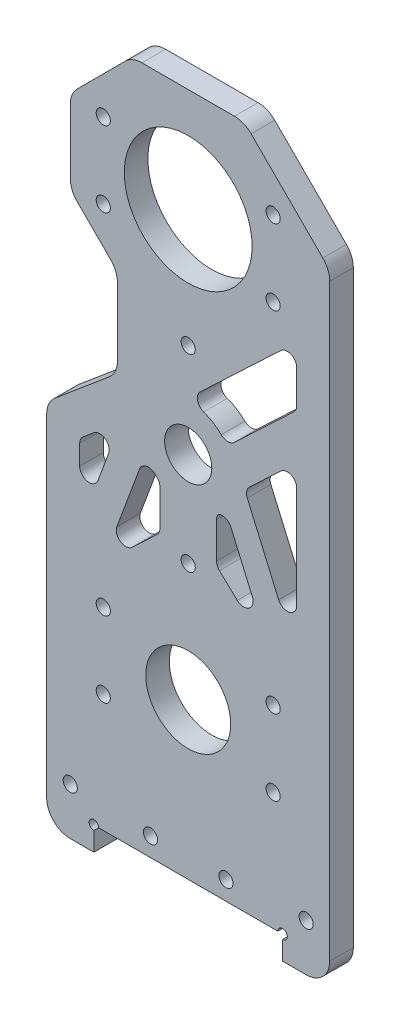
SolidWorks part; units mm, degrees
ref_plane "前视基准面" through (0, 0, 0) normal (0, 0, 1) x (1, 0, 0)
ref_plane "上视基准面" through (0, 0, 0) normal (0, 1, 0) x (1, 0, 0)
ref_plane "右视基准面" through (0, 0, 0) normal (1, 0, 0) x (0, 0, -1)
other "Configuration Table"
sketch "草图1" plane through (0, 0, 0) normal (0, 0, 1) x (1, 0, 0)
  line L1 (30, 0) -> (-30, 0)
  line L2 (30, 0) -> (30, 150)
  line L3 (30, 150) -> (-30, 150)
  line L4 (-30, 0) -> (-30, 150)
  point P6 (0, 0)
  dimension "D1" = 60
  dimension "D2" = 150
extrude "凸台-拉伸1" add sketch "草图1" along normal blind 5
sketch "草图2" plane through (0, 0, 5) normal (0, 0, 1) x (1, 0, 0)
  line L0 (-30, 0) -> (30, 0) construction
  line L1 (-20, 0) -> (20, 0)
  line L2 (-20, 0) -> (-20, 5)
  line L3 (-20, 5) -> (20, 5)
  line L4 (20, 0) -> (20, 5)
  line L5 (-25, 10) -> (25, 10) construction
  line L6 (-30, 150) -> (-30, 0) construction
  line L7 (30, 0) -> (30, 150) construction
  line L8 (0, 0) -> (0, 9) construction
  line L9 (-8, 9) -> (8, 9) construction
  circle A0 centre (-25, 10) radius 1.5
  circle A1 centre (25, 10) radius 1.5
  circle A2 centre (20, 5) radius 1
  circle A3 centre (-20, 5) radius 1
  circle A4 centre (8, 9) radius 1.5
  circle A5 centre (-8, 9) radius 1.5
  point P21 (0, 9)
  dimension "D1" = 3
  dimension "D3" = 2
  dimension "D10" = 3
  dimension "D2" = 5
  dimension "D4" = 10
  dimension "D5" = 10
  dimension "D6" = 5
  dimension "D7" = 5
  dimension "D8" = 10
  dimension "D9" = 16
  dimension "D11" = 4
extrude "切除-拉伸1" cut sketch "草图2" against normal blind 5
sketch "草图4" plane through (0, 0, 5) normal (0, 0, 1) x (1, 0, 0)
  line L0 (0, 0) -> (0, 150) construction
  line L1 (30, 150) -> (-30, 150) construction
  line L2 (-19, 5) -> (19, 5) construction
  circle A0 centre (0, 128) radius 13.55
  circle A1 centre (0, 38) radius 9
  dimension "D1" = 90
  dimension "D2" = 27.1
  dimension "D4" = 18
  dimension "D3" = 33
extrude "弹链孔" cut sketch "草图4" against normal through all
sketch "草图5" plane through (0, 0, 5) normal (0, 0, 1) x (1, 0, 0)
  line L0 (-19.1511, 111.9303) -> (-15, 106.9832) construction
  line L1 (-30, 150) -> (-30, 0) construction
  line L2 (-15, 106.9832) -> (-15, 90.3497)
  line L3 (-15, 90.3497) -> (-30, 77.7632)
  line L4 (-30, 124.8595) -> (-19.1511, 111.9303) construction
  line L5 (30, 150) -> (-30, 150) construction
  line L6 (-30, 124.8595) -> (-30, 77.7632)
  line L7 (-30, 124.8595) -> (-30, 150)
  line L8 (-30, 150) -> (-11.8743, 150)
  line L9 (0, 128) -> (-19.1511, 111.9303) construction
  line L10 (-19.1511, 111.9303) -> (-65.3229, 73.1876) construction
  line L11 (-52.9813, 58.4796) -> (-30, 77.7632) construction
  line L12 (-65.3229, 73.1876) -> (-52.9813, 58.4796) construction
  line L13 (-22, 116.1257) -> (-15, 109.1257)
  line L14 (-22, 116.1257) -> (-22, 139.8743) construction
  line L15 (-22, 139.8743) -> (-11.8743, 150)
  line L16 (-15, 109.1257) -> (-15, 106.9832)
  line L17 (11.8743, 150) -> (30, 131.8743)
  line L18 (30, 0) -> (30, 150) construction
  line L19 (11.8743, 150) -> (30, 150)
  line L20 (30, 150) -> (30, 131.8743)
  line L21 (-22, 139.8743) -> (-25, 136.8743)
  line L22 (-25, 136.8743) -> (-25, 119.1257)
  line L23 (-22, 116.1257) -> (-25, 119.1257)
  arc A0 (-11.8743, 150) -> (-19.1511, 111.9303) centre (0, 128) ccw construction
  dimension "D1" = 40
  dimension "D2" = 25
  dimension "D3" = 15
  dimension "D4" = 30
  dimension "D5" = 19.2
  dimension "D6" = 135
  dimension "D7" = 135
  dimension "D8" = 45
extrude "切除-拉伸2" cut sketch "草图5" against normal through all
sketch "草图6" plane through (0, 0, 5) normal (0, 0, 1) x (1, 0, 0)
  line L0 (0, 83) -> (0, 128) construction
  circle A0 centre (0, 83) radius 5
  dimension "D2" = 10
  dimension "D1" = 45
extrude "切除-拉伸3" cut sketch "草图6" against normal through all
sketch "草图7" plane through (0, 0, 5) normal (0, 0, 1) x (1, 0, 0)
  line L0 (0, 63) -> (0, 103) construction
  line L1 (-18, 136) -> (18, 136) construction
  line L2 (-18, 136) -> (-18, 120) construction
  line L3 (-18, 120) -> (18, 120) construction
  line L4 (18, 136) -> (18, 120) construction
  line L5 (-18, 136) -> (18, 120) construction
  line L6 (-18, 120) -> (18, 136) construction
  line L8 (-18, 46) -> (18, 46) construction
  line L9 (-18, 46) -> (-18, 30) construction
  line L10 (-18, 30) -> (18, 30) construction
  line L11 (18, 46) -> (18, 30) construction
  line L12 (-18, 46) -> (18, 30) construction
  line L13 (-18, 30) -> (18, 46) construction
  circle A0 centre (18, 136) radius 1.5
  circle A1 centre (-18, 136) radius 1.5
  circle A2 centre (-18, 120) radius 1.5
  circle A3 centre (18, 120) radius 1.5
  circle A4 centre (0, 63) radius 1.5
  circle A6 centre (0, 103) radius 1.5
  circle A7 centre (0, 83) radius 5 construction
  circle A8 centre (-18, 46) radius 1.5
  circle A9 centre (-18, 30) radius 1.5
  circle A10 centre (18, 46) radius 1.5
  circle A11 centre (18, 30) radius 1.5
  point P0 (0, 128)
  point P14 (0, 83)
  point P19 (0, 38)
  dimension "D3" = 3
  dimension "D5" = 3
  dimension "D8" = 3
  dimension "D1" = 36
  dimension "D2" = 16
  dimension "D4" = 40
  dimension "D6" = 36
  dimension "D7" = 16
extrude "切除-拉伸4" cut sketch "草图7" against normal through all
sketch "草图8" plane through (0, 0, 0) normal (0, 0, -1) x (-1, 0, 0)
  circle A0 centre (-18, 136) radius 4.5
  circle A1 centre (18, 136) radius 4.5
  circle A2 centre (-18, 120) radius 4.5
  circle A3 centre (18, 120) radius 4.5
  circle A4 centre (0, 103) radius 4.5
  circle A5 centre (0, 63) radius 4.5
  dimension "D1" = 9
extrude "切除-拉伸5" cut sketch "草图8" against normal blind 2
sketch "草图9" plane through (0, 0, 5) normal (0, 0, 1) x (1, 0, 0)
  line L0 (-9.6216, 85.7248) -> (-23, 74.499)
  line L1 (-23, 74.499) -> (-23, 49.5307)
  line L3 (-23, 49.5307) -> (-6, 65.5863)
  line L7 (6, 65.5863) -> (23, 49.5307)
  line L8 (23, 49.5307) -> (23, 92.9752)
  line L10 (8.241, 88.6645) -> (23, 102.6036)
  line L11 (23, 102.6036) -> (23, 115.0938)
  line L12 (23, 115.0938) -> (-0.402, 92.9919)
  line L13 (0, 63) -> (-18, 46) construction
  line L14 (-30, 77.7632) -> (-15, 90.3497) construction
  line L15 (-30, 77.7632) -> (-30, 0) construction
  line L16 (0, 83) -> (0, 63) construction
  line L17 (-6, 83) -> (-6, 63)
  line L18 (6, 83) -> (6, 63)
  line L19 (0, 63) -> (18, 46) construction
  line L20 (30, 0) -> (30, 131.8743) construction
  line L21 (23, 92.9752) -> (9.6461, 80.3631)
  line L22 (0, 103) -> (18, 120) construction
  line L23 (9.6461, 80.3631) -> (23, 49.5307) construction
  line L24 (6.8932, 79.1708) -> (20.2471, 48.3384)
  line L25 (12.399, 81.5554) -> (25.7529, 50.723)
  line L26 (12.399, 81.5554) -> (11.9663, 82.5544)
  line L27 (-9.6216, 85.7248) -> (-23, 49.5307) construction
  line L28 (-12.4355, 86.765) -> (-25.8139, 50.5708)
  line L29 (-6.8077, 84.6847) -> (-20.1861, 48.4906)
  circle A2 centre (0, 83) radius 10
  dimension "D1" = 6
  dimension "D4" = 20
  dimension "D2" = 7
  dimension "D3" = 7
  dimension "D7" = 6
  dimension "D8" = 7
  dimension "D9" = 7
  dimension "D10" = 7
  dimension "D11" = 7
  dimension "D5" = 6
  dimension "D6" = 6
  dimension "D12" = 3
  dimension "D13" = 3
  dimension "D14" = 3
  dimension "D15" = 3
extrude "切除-拉伸6" cut sketch "草图9" against normal through all contours L28 L0 L1 | A2 L29 L3 L17 | A2 L18 L7 L24 | L26 L25 L8 L21 | A2 L10 L11 L12
fillet "圆角3" radius 2 18 edges at (-6, 75, 2.5) (-6, 65.5863, 2.5) (-18.0863, 54.1715, 2.5) (-9.0235, 78.69, 2.5) (-0.402, 92.9919, 2.5) (23, 115.0938, 2.5) (23, 102.6036, 2.5) (8.241, 88.6645, 2.5) (-23, 58.1837, 2.5) (-14.258, 81.8345, 2.5) (11.9663, 82.5544, 2.5) (23, 92.9752, 2.5) (23, 57.0791, 2.5) (7.8937, 76.8608, 2.5) (17.4677, 54.7557, 2.5) (6, 65.5863, 2.5) (6, 75, 2.5) (-23, 74.499, 2.5)
fillet "圆角4" radius 5 10 edges at (-15, 90.3497, 2.5) (-15, 109.1257, 2.5) (-11.8743, 150, 2.5) (11.8743, 150, 2.5) (30, 131.8743, 2.5) (30, 0, 2.5) (-30, 77.7632, 2.5) (-30, 0, 2.5) (-25, 119.1257, 2.5) (-25, 136.8743, 2.5)
